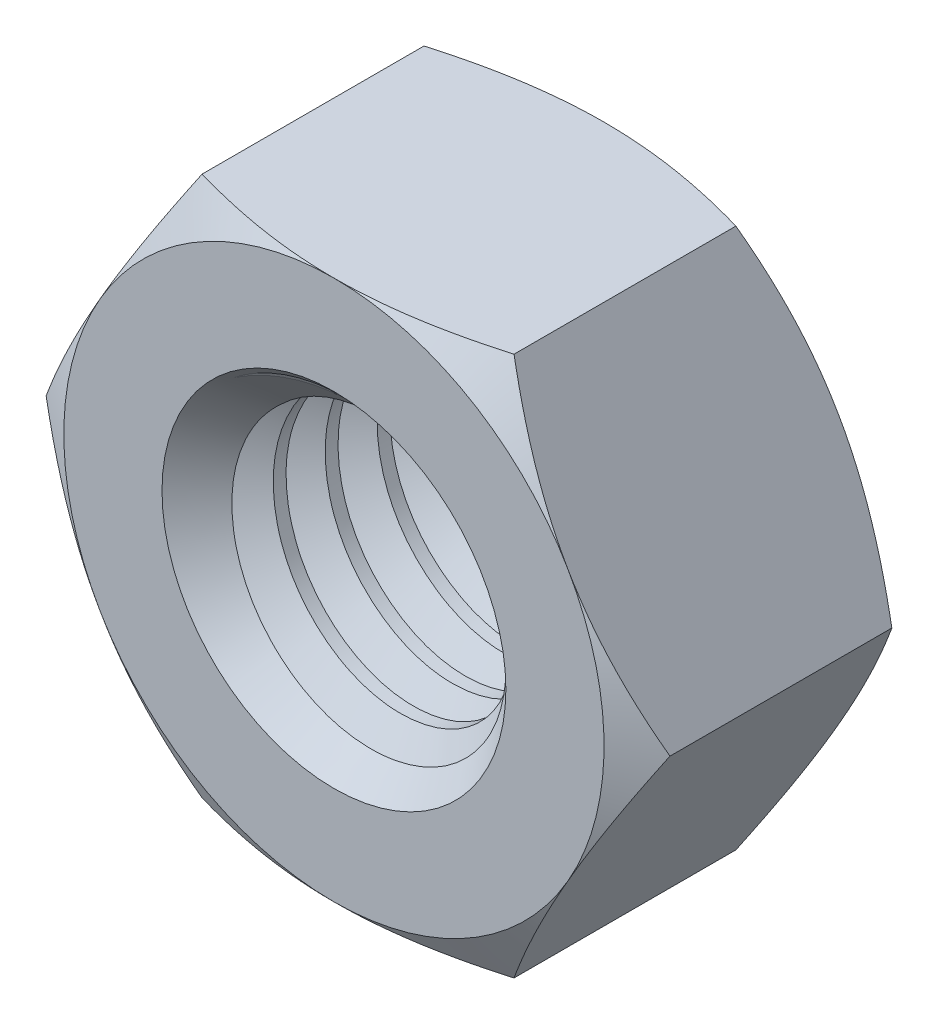
SolidWorks part; units mm, degrees
ref_plane "Front" through (0, 0, 0) normal (0, 0, 1) x (1, 0, 0)
ref_plane "Top" through (0, 0, 0) normal (0, 1, 0) x (1, 0, 0)
ref_plane "Right" through (0, 0, 0) normal (1, 0, 0) x (0, 0, -1)
sketch "Çizim1" plane through (0, 0, 0) normal (0, 0, 1) x (1, 0, 0)
  line L1 (7.5056, 0) -> (3.7528, 6.5)
  line L2 (3.7528, 6.5) -> (-3.7528, 6.5)
  line L3 (-3.7528, 6.5) -> (-7.5056, 0)
  line L4 (-7.5056, 0) -> (-3.7528, -6.5)
  line L5 (-3.7528, -6.5) -> (3.7528, -6.5)
  line L6 (3.7528, -6.5) -> (7.5056, 0)
  circle A0 centre (0, 0) radius 6.5 construction
  dimension "D1" = 13
extrude "Yükseklik-Ekstrüzyon1" add sketch "Çizim1" along normal blind 6.5
sketch "Çizim2" plane through (0, 0, 6.5) normal (0, 0, 1) x (1, 0, 0)
  circle A0 centre (0, 0) radius 6.5
extrude "Kes-Ekstrüzyon1" cut sketch "Çizim2" against normal blind 6.5 draft 60 flip side to cut
sketch "Çizim3" plane through (0, 0, 0) normal (0, 0, -1) x (-1, 0, 0)
  circle A0 centre (0, 0) radius 6.5
extrude "Kes-Ekstrüzyon2" cut sketch "Çizim3" against normal blind 6.5 draft 60 flip side to cut
sketch "Çizim4" plane through (0, 0, 0) normal (0, 0, -1) x (-1, 0, 0)
  circle A0 centre (0, 0) radius 3.1875
  dimension "D1" = 6.375
extrude "Kes-Ekstrüzyon3" cut sketch "Çizim4" against normal blind 6.5
chamfer "Pah1" distance 0.95 angle 45 2 edges at (-3.1875, 0, 6.5) (-3.1875, 0, 0)
sketch "Çizim5" plane through (0, 0, 6.5) normal (0, 0, 1) x (1, 0, 0)
  circle A0 centre (0, 0) radius 3.1875
curve "Helis/Spiral1" pitch 1.25 height 8 turns 6.4
ref_plane "Düzlem1" through (2.5787, 1.8736, -1.5) normal (0.5866, -0.8074, -0.0623) x (-0.8098, -0.5849, -0.0451)
sketch "Çizim6" plane through (2.5787, 1.8736, -1.5) normal (0.5866, -0.8074, -0.0623) x (-0.8098, -0.5849, -0.0451)
  line L0 (0.2815, 0.6316) -> (0.2815, -0.6316)
  line L1 (-0.8125, 0) -> (0.2815, -0.6316)
  line L3 (0.2815, 0.6316) -> (-0.8125, 0)
  line L5 (0.4063, 0) -> (0.4062, 0.7036) [skipped]
  circle A0 centre (0, 0) radius 0.4063 construction
  dimension "D1" = 0.8125
sweep "Kes-Süpür1" cut profiles "Çizim6" path "Helis/Spiral1"
